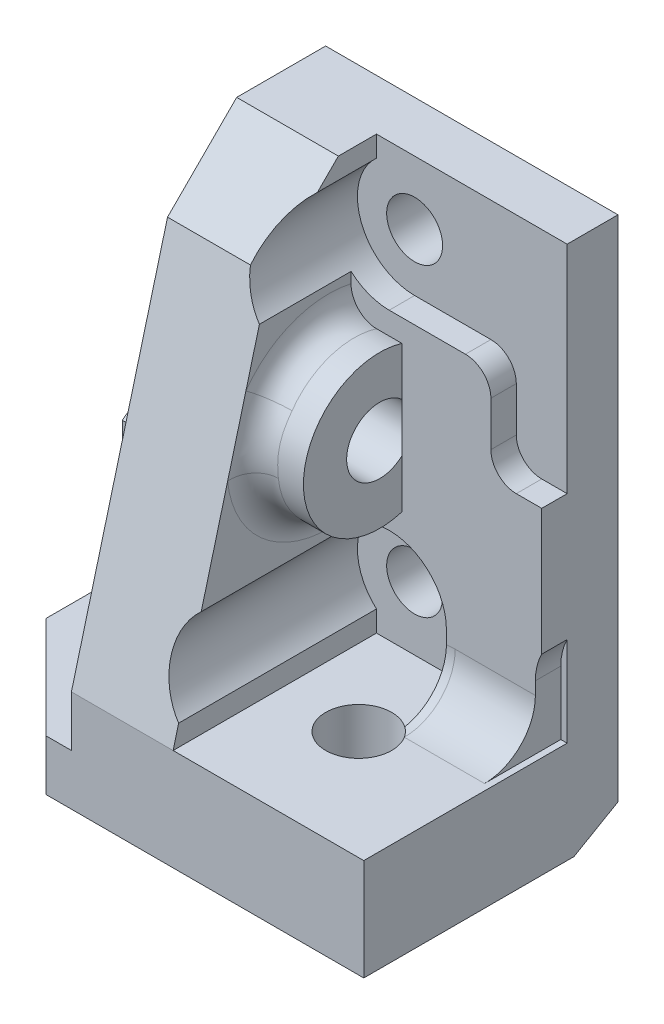
SolidWorks part; units mm, degrees
ref_plane "前视基准面" through (0, 0, 0) normal (0, 0, 1) x (1, 0, 0)
ref_plane "上视基准面" through (0, 0, 0) normal (0, 1, 0) x (1, 0, 0)
ref_plane "右视基准面" through (0, 0, 0) normal (1, 0, 0) x (0, 0, -1)
sketch "草图1" plane through (0, 0, 0) normal (0, 0, 1) x (1, 0, 0)
  line L0 (0, 0) -> (8, 0) construction
  line L1 (8, 0) -> (8, 12) construction
  line L2 (8, 12) -> (0, 12) construction
  line L3 (0, 12) -> (0, 0) construction
  line L4 (0, 6) -> (8, 6) construction
  line L5 (-7.5, 14.5) -> (15.5, 14.5)
  line L6 (-7.5, 14.5) -> (-7.5, -2.5)
  line L7 (-7.5, -2.5) -> (15.5, -2.5)
  line L8 (15.5, 14.5) -> (15.5, -2.5)
  line L9 (4, 12) -> (4, 14.5) construction
  circle A0 centre (0, 0) radius 1.1
  circle A1 centre (8, 0) radius 1.1
  circle A2 centre (0, 12) radius 1.1
  circle A3 centre (8, 12) radius 1.1
  dimension "D1" = 2.2
  dimension "D2" = 12
  dimension "D3" = 8
  dimension "D4" = 17
  dimension "D5" = 23
extrude "凸台-拉伸1" add sketch "草图1" along normal blind 3
sketch "草图2" plane through (-7.5, 0, 0) normal (-1, 0, 0) x (0, 0, 1)
  line L0 (5.5, 14.5) -> (10, -2.5)
  line L1 (0, 14.5) -> (5.5, 14.5)
  line L2 (0, 14.5) -> (0, -2.5)
  line L3 (0, -2.5) -> (5.5, -2.5)
  line L4 (5.5, 14.5) -> (5.5, -2.5) construction
  line L5 (10, -2.5) -> (5.5, -2.5)
  dimension "D1" = 5.5
  dimension "D2" = 4.5
extrude "凸台-拉伸2" add sketch "草图2" against normal blind 6
sketch "草图3" plane through (0, 0, 3) normal (0, 0, 1) x (1, 0, 0)
  circle A0 centre (0, 12) radius 2.25
  circle A1 centre (8, 12) radius 2.25
  circle A2 centre (0, 12) radius 1.1 construction
  circle A3 centre (0, 0) radius 2.25
  circle A4 centre (8, 0) radius 2.25
  dimension "D1" = 4.5
extrude "切除-拉伸1" cut sketch "草图3" against normal blind 1 and the other way through all
sketch "草图4" plane through (0, 0, 3) normal (0, 0, 1) x (1, 0, 0)
  line L0 (15.5, 14.5) -> (-1.5, 14.5) construction
  line L1 (11, 14.5) -> (15.5, 14.5)
  line L2 (11, 14.5) -> (11, -2.5)
  line L3 (11, -2.5) -> (15.5, -2.5)
  line L4 (15.5, 14.5) -> (15.5, -2.5)
  dimension "D1" = 4.5
extrude "切除-拉伸2" cut sketch "草图4" against normal up to next
sketch "草图5" plane through (-7.5, 0, 0) normal (-1, 0, 0) x (0, 0, 1)
  line L4 (0, 14.5) -> (0, -2.5)
  line L5 (0, -2.5) -> (10, -2.5)
  line L6 (10, -2.5) -> (5.5, 14.5)
  line L7 (5.5, 14.5) -> (0, 14.5)
  line L8 (0, 14.5) -> (0, -2.5)
  line L9 (0, -2.5) -> (10, -2.5)
  line L11 (5.5, 14.5) -> (0, 14.5)
  line L12 (10, -2.5) -> (5.5, 14.5)
  dimension "D1" = 0
extrude "切除-拉伸3" cut sketch "草图5" against normal blind 2
sketch "草图6" plane through (-5.5, 0, 0) normal (-1, 0, 0) x (0, 0, 1)
  line L0 (2.75, 14.5) -> (5, -2.5) construction
  line L1 (5.5, 14.5) -> (0, 14.5) construction
  line L2 (0, -2.5) -> (10, -2.5) construction
  circle A1 centre (3.875, 6) radius 1.3
  dimension "D2" = 2.6
extrude "切除-拉伸4" cut sketch "草图6" against normal blind 4
sketch "草图7" plane through (0, -2.5, 0) normal (0, -1, 0) x (1, 0, 0)
  line L1 (-5.5, 10) -> (11, 10)
  line L2 (-5.5, 10) -> (-5.5, 0)
  line L3 (-5.5, 0) -> (11, 0)
  line L4 (11, 10) -> (11, 0)
extrude "凸台-拉伸3" add sketch "草图7" along normal blind 4
sketch "草图8" plane through (0, -6.5, 0) normal (0, -1, 0) x (1, 0, 0)
  line L0 (-5.5, 5.7) -> (11, 5.7) construction
  line L1 (-5.5, 10) -> (-5.5, 0) construction
  line L2 (11, 0) -> (11, 10) construction
  line L3 (-5.5, 0) -> (11, 0) construction
  circle A0 centre (1.5, 5.7) radius 1.3
  dimension "D2" = 2.6
  dimension "D3" = 7
  dimension "D1" = 5.7
extrude "切除-拉伸5" cut sketch "草图8" against normal up to surface (4 mm away) up to face at (4.75, -2.5, 6.5)
chamfer "倒角1" distance 1 angle 60 1 edges at (2.75, -6.5, 0) first distance on face at (1.1, 0, 0)
chamfer "倒角2" distance 4 angle 45 1 edges at (11, -4.5, 10)
sketch "草图9" plane through (0, 0, 3) normal (0, 0, 1) x (1, 0, 0)
  line L0 (-1.5, 13.6771) -> (-1.5, 14.5)
  line L1 (-1.5, 14.5) -> (2.25, 14.5)
  line L2 (11, 14.5) -> (-1.5, 14.5) construction
  line L3 (2.25, 14.5) -> (2.25, 12)
  line L4 (5.75, 12) -> (5.75, 14.5)
  line L5 (5.75, 14.5) -> (11, 14.5)
  line L6 (11, 14.5) -> (11, 9.75)
  line L7 (11, 14.5) -> (11, -2.5) construction
  line L8 (11, 9.75) -> (8, 9.75)
  line L9 (2.25, 0) -> (2.25, -2.5)
  line L10 (7, -2.5) -> (-1.5, -2.5) construction
  line L11 (2.25, -2.5) -> (-1.5, -2.5)
  line L12 (-1.5, -2.5) -> (-1.5, -1.6771)
  line L13 (5.75, 0) -> (5.75, -2.5)
  line L14 (-1.5, -2.5) -> (11, -2.5) construction
  line L15 (5.75, -2.5) -> (11, -2.5)
  line L16 (11, -2.5) -> (11, 2.25)
  line L17 (11, 2.25) -> (8, 2.25)
  arc A0 (-1.5, 10.3229) -> (-1.5, 13.6771) centre (0, 12) ccw construction
  circle A1 centre (8, 12) radius 2.25 construction
  circle A2 centre (8, 12) radius 2.25 construction
  arc A3 (2.25, 12) -> (-1.5, 13.6771) centre (0, 12) ccw
  arc A4 (8, 9.75) -> (5.75, 12) centre (8, 12) ccw
  arc A5 (-1.5, -1.6771) -> (-1.5, 1.6771) centre (0, 0) ccw construction
  circle A6 centre (8, 0) radius 2.25 construction
  circle A7 centre (8, 0) radius 2.25 construction
  arc A8 (5.75, 0) -> (8, 2.25) centre (8, 0) ccw
  arc A9 (-1.5, -1.6771) -> (2.25, 0) centre (0, 0) ccw
extrude "切除-拉伸6" cut sketch "草图9" against normal up to surface (1 mm away) up to face at (1.1, 12, 2)
fillet "圆角1" radius 2 1 edges at (11, 14.5, 1)
sketch "草图10" plane through (0, 0, 2) normal (0, 0, 1) x (1, 0, 0)
  line L0 (5.75, 14.5) -> (2.25, 14.5) construction
  line L1 (4, 14.5) -> (11, 14.5)
  line L2 (4, 9.75) -> (4, 6)
  line L3 (4, 6) -> (11, 6)
  line L4 (11, 14.5) -> (11, 6)
  line L5 (11, 9.75) -> (11, 2.25) construction
  line L6 (0, 9.75) -> (4, 9.75)
  line L7 (2.25, 14.5) -> (2.25, 12) construction
  line L8 (2.25, 14.5) -> (4, 14.5)
  line L9 (2.25, 14.5) -> (2.25, 12)
  arc A0 (-1.5, 13.6771) -> (2.25, 12) centre (0, 12) ccw construction
  arc A1 (-1.5, 10.3229) -> (2.25, 12) centre (0, 12) ccw construction
  arc A2 (0, 9.75) -> (2.25, 12) centre (0, 12) ccw
extrude "切除-拉伸7" cut sketch "草图10" along normal up to next
fillet "圆角2" radius 1 2 edges at (4, 6, 2.5) (4, 9.75, 2.5)
chamfer "倒角3" distance 2 angle 45 1 edges at (-3.5, 14.5, 5.5) first distance on face at (0.6667, 14.5, 2.5)
sketch "草图11" plane through (0, -6.5, 0) normal (0, -1, 0) x (1, 0, 0)
  line L0 (7, 10) -> (-5.5, 10) construction
  line L1 (6, 10) -> (11, 10)
  line L2 (6, 10) -> (6, 0)
  line L3 (6, 0) -> (11, 0)
  line L4 (11, 10) -> (11, 0)
  dimension "D1" = 5
extrude "切除-拉伸8" cut sketch "草图11" against normal up to next
sketch "草图12" plane through (-5.5, 0, 0) normal (-1, 0, 0) x (0, 0, 1)
  line L0 (0, -5.5) -> (1.7321, -6.5)
  line L1 (1.7321, -6.5) -> (3, -6.5)
  line L5 (3, 1.5) -> (0, 1.5)
  line L6 (0, 1.5) -> (0, -5.5)
  line L7 (3, -6.5) -> (3, 1.5)
  dimension "D1" = 8
  dimension "D2" = 3
extrude "凸台-拉伸4" add sketch "草图12" along normal blind 5
sketch "草图13" plane through (0, 0, 3) normal (0, 0, 1) x (1, 0, 0)
  circle A0 centre (-8, 0) radius 1.1
  circle A1 centre (0, 0) radius 1.1 construction
  dimension "D1" = 8
extrude "切除-拉伸9" cut sketch "草图13" against normal up to next
sketch "草图14" plane through (0, 0, 3) normal (0, 0, 1) x (1, 0, 0)
  circle A0 centre (-8, 0) radius 2.25
  arc A1 (2.25, 0) -> (-1.5, -1.6771) centre (0, 0) ccw construction
extrude "切除-拉伸10" cut sketch "草图14" against normal up to surface (1 mm away) up to face at (1.1, 0, 2)
sketch "草图16" plane through (-10.5, 0, 0) normal (-1, 0, 0) x (0, 0, 1)
  line L0 (2, 1.5) -> (0, 3)
  line L1 (3, 1.5) -> (0, 1.5) construction
  line L2 (0, 3) -> (0, 1.5)
  line L4 (0, 1.5) -> (2, 1.5)
  dimension "D1" = 1.5
  dimension "D2" = 2
extrude "凸台-拉伸6" add sketch "草图16" against normal up to surface (5 mm away) up to face at (-5.5, 3.535, 4.465)
fillet "圆角3" radius 2 1 edges at (-10.5, 1.5, 2.5)
sketch "草图15" plane through (0, 0, 3) normal (0, 0, 1) x (1, 0, 0)
  line L0 (-5.5, -6.5) -> (-5.5, -2.5) construction
  line L1 (-10.5, -6.5) -> (-5.5, -6.5)
  line L2 (-10.5, -6.5) -> (-10.5, -4.5)
  line L3 (-10.5, -4.5) -> (-5.5, -4.5)
  line L4 (-5.5, -6.5) -> (-5.5, -4.5)
  dimension "D1" = 2
extrude "凸台-拉伸5" add sketch "草图15" along normal up to surface (7 mm away) up to face at (-0.1, -4.1, 10)
sketch "草图17" plane through (-10.5, 0, 0) normal (-1, 0, 0) x (0, 0, 1)
  line L0 (2, 1.5) -> (3, 0.75)
  line L1 (3, -4.5) -> (3, 1.5) construction
  line L2 (3, 0.75) -> (2, 1.5) construction
  line L3 (3, 0.75) -> (3, 1.5)
  line L4 (3, 1.5) -> (2, 1.5)
extrude "切除-拉伸11" cut sketch "草图17" against normal up to surface (5 mm away) up to face at (-5.5, 4.7, 3.875)
chamfer "倒角4" distance 4 angle 45 1 edges at (-10.5, -5.5, 10)
sketch "草图18" plane through (-5.5, 0, 0) normal (-1, 0, 0) x (0, 0, 1)
  circle A0 centre (3.875, 6) radius 3
  circle A1 centre (3.875, 6) radius 1.3 construction
  circle A2 centre (3.875, 6) radius 1.3
  dimension "D1" = 6
extrude "凸台-拉伸7" add sketch "草图18" against normal blind 6
sketch "草图19" plane through (-1.5, 0, 0) normal (-1, 0, 0) x (0, 0, 1)
  line L1 (3, 5.0386) -> (3, 6.9614)
  line L2 (3, 5.0386) -> (3, 6.9614)
  arc A1 (3, 6.9614) -> (3, 5.0386) centre (3.875, 6) ccw
  arc A2 (3, 6.9614) -> (3, 5.0386) centre (3.875, 6) ccw
  dimension "D1" = 0
extrude "切除-拉伸12" cut sketch "草图19" against normal up to surface (2 mm away) up to face at (0.5, 6, 4.5125)
fillet "圆角4" radius 1 1 edges at (-1.5, 6, 6.875)
fillet "圆角5" radius 2 1 edges at (4, -2.5, 3)
